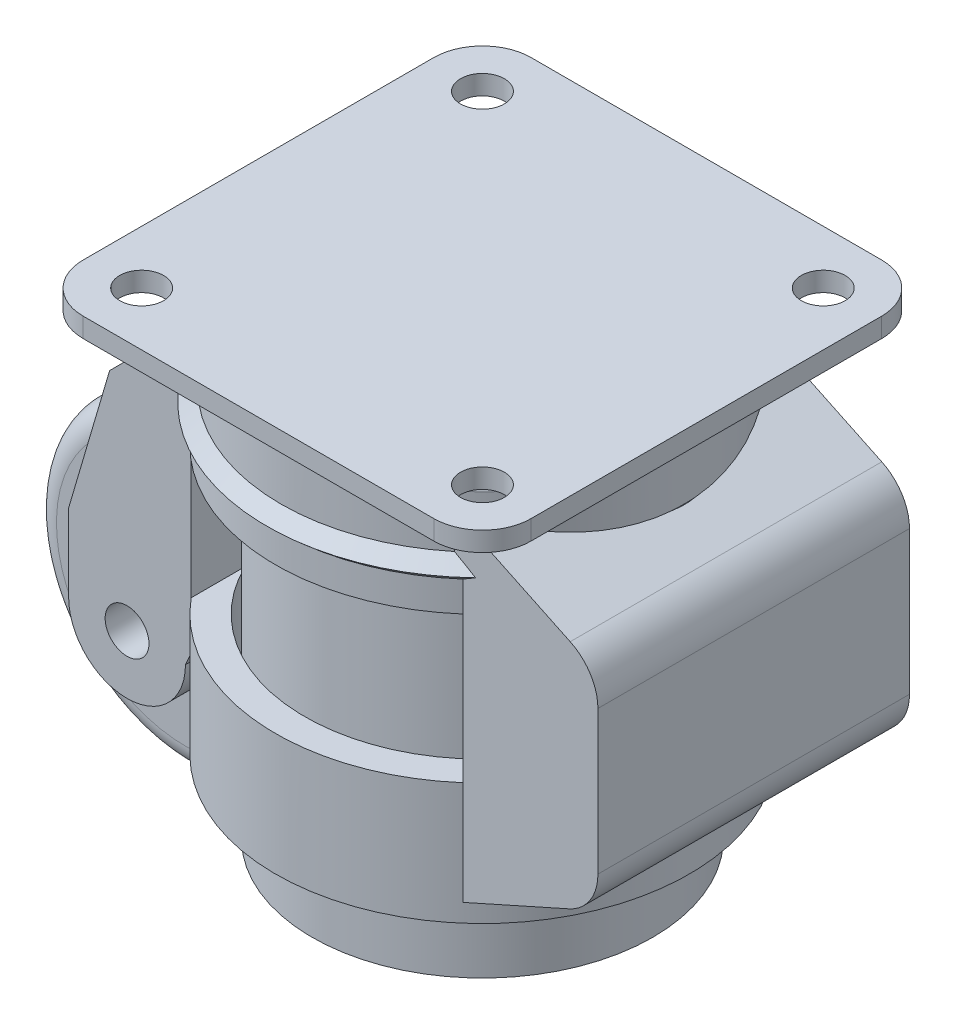
SolidWorks part; units mm, degrees
ref_plane "前视基准面" through (0, 0, 0) normal (0, 0, 1) x (1, 0, 0)
ref_plane "上视基准面" through (0, 0, 0) normal (0, 1, 0) x (1, 0, 0)
ref_plane "右视基准面" through (0, 0, 0) normal (1, 0, 0) x (0, 0, -1)
sketch "草图1" plane through (0, 0, 0) normal (0, 0, 1) x (1, 0, 0)
  line L2 (46, 0) -> (46, 4)
  line L3 (-46, 4) -> (-46, 0)
  line L4 (-46, 0) -> (46, 0)
  line L5 (-46, 4) -> (46, 4)
extrude "凸台-拉伸1" add sketch "草图1" along normal blind 46 and the other way blind 46
sketch "草图2" plane through (0, 4, 0) normal (0, 1, 0) x (1, 0, 0)
  circle A0 centre (35, 35) radius 4.5
  circle A1 centre (-35, 35) radius 4.5
  circle A2 centre (-35, -35) radius 4.5
  circle A3 centre (35, -35) radius 4.5
  dimension "D1" = 35
  dimension "D2" = 35
  dimension "D3" = 2
  dimension "D4" = 2
extrude "切除-拉伸1" cut sketch "草图2" against normal through all
fillet "圆角1" radius 10 4 edges at (46, 2, -46) (-46, 2, -46) (46, 2, 46) (-46, 2, 46)
sketch "草图3" plane through (0, 0, 0) normal (0, 0, 1) x (1, 0, 0)
  line L0 (0, 0) -> (30, 0)
  line L1 (-36, 0) -> (36, 0) construction
  line L2 (30, 0) -> (30, -2)
  line L3 (30, -2) -> (40.3924, -2)
  line L4 (41.3924, -3) -> (41.3924, -13.7394)
  line L6 (42.5, -17.7944) -> (42.5, -79)
  line L7 (41.3924, -13.7394) -> (44.2632, -16.2515)
  line L8 (42.5, -79) -> (0, -79)
  line L9 (0, -79) -> (0, 0)
  line L10 (36, 4) -> (-36, 4) construction
  line L11 (42.5, -17.7944) -> (44.2632, -16.2515)
  arc A0 (41.3924, -3) -> (40.3924, -2) centre (40.3924, -3) ccw
  dimension "D4" = 1
  dimension "D1" = 30
  dimension "D2" = 2
  dimension "D3" = 83
  dimension "D5" = 42.5
revolve "旋转1" add sketch "草图3" angle 360 about L9
sketch "草图4" plane through (0, 0, 0) normal (0, 0, 1) x (1, 0, 0)
  line L0 (-41.3924, -13.7394) -> (-49.5804, -21.9716)
  line L1 (-49.5804, -21.9716) -> (-58, -50.6155)
  line L3 (-41.3924, -13.7394) -> (-44.2632, -16.2515) construction
  line L5 (-27.053, -50.6155) -> (-9.2251, -27.0175)
  line L6 (-9.2251, -27.0175) -> (-28.47, -9.3947)
  line L7 (-28.47, -9.3947) -> (-41.3924, -13.7394)
  line L9 (36, 4) -> (-36, 4) construction
  line L10 (-58, -66.5) -> (-58, -50.6155)
  line L11 (-34, -66.5) -> (-27.053, -50.6155)
  arc A0 (-58, -66.5) -> (-34, -66.5) centre (-46, -66.5) ccw
  dimension "D1" = 70.5
  dimension "D2" = 46
extrude "凸台-拉伸2" add sketch "草图4" along normal blind 27 and the other way blind 27
sketch "草图5" plane through (0, -79, 0) normal (0, -1, 0) x (1, 0, 0)
  circle A0 centre (0, 0) radius 36.5
extrude "切除-拉伸2" cut sketch "草图5" against normal blind 68.6 and the other way blind 32
sketch "草图8" plane through (0, 0, 0) normal (0, 0, 1) x (1, 0, 0)
  line L0 (36, 4) -> (-36, 4) construction
  line L1 (-67.3863, -34) -> (0, -34)
  line L2 (-67.3863, -34) -> (-67.3863, -109.3295)
  line L3 (-67.3863, -109.3295) -> (0, -109.3295)
  line L4 (0, -34) -> (0, -109.3295)
  dimension "D1" = 38
extrude "切除-拉伸3" cut sketch "草图8" against normal blind 15 and the other way blind 15
sketch "草图9" plane through (0, 0, 27) normal (0, 0, 1) x (1, 0, 0)
  circle A0 centre (-46, -66.5) radius 4.5
extrude "切除-拉伸4" cut sketch "草图9" against normal through all
sketch "草图11" plane through (0, 0, 0) normal (0, 0, 1) x (1, 0, 0)
  circle A0 centre (-46, -66.5) radius 31.5
extrude "凸台-拉伸3" add sketch "草图11" along normal blind 15 and the other way blind 15
fillet "圆角2" radius 5 2 edges at (-48.6619, -97.8873, 15) (-48.6619, -97.8873, -15)
sketch "草图13" plane through (0, -79, 0) normal (0, -1, 0) x (1, 0, 0)
  line L0 (-12, 17.5) -> (-30.3109, 17.5)
  line L1 (-12, 17.5) -> (-12, -17.5)
  line L2 (-12, -17.5) -> (-30.3109, -17.5)
  arc A0 (-30.3109, -17.5) -> (-30.3109, 17.5) centre (0, 0) ccw
  dimension "D1" = 17.5
  dimension "D3" = 70
  dimension "D2" = 17.5
  dimension "D4" = 12
sketch "草图14" plane through (0, 0, 0) normal (0, 0, 1) x (1, 0, 0)
  line L0 (22.6517, -4.8219) -> (55.7189, -20.614)
  line L1 (55.7189, -20.614) -> (55.7189, -62.8829)
  line L2 (55.7189, -62.8829) -> (18.46, -79.5439)
  line L3 (18.46, -79.5439) -> (22.6517, -4.8219)
extrude "凸台-拉伸6" add sketch "草图14" along normal blind 32 and the other way blind 32
sketch "草图16" plane through (0, -79, 0) normal (0, -1, 0) x (1, 0, 0)
  line L1 (-22.8896, 28.4309) -> (0.9181, 28.4309)
  line L4 (0.9181, 28.4309) -> (0.9181, -36.4885)
  arc A0 (0.9181, -36.4885) -> (-22.8896, 28.4309) centre (0, 0) ccw
extrude "切除-拉伸6" cut sketch "草图16" against normal up to surface (68.6 mm away) up to face at (-7.0806, -10.4, 0)
sketch "草图17" plane through (0, 0, 32) normal (0, 0, 1) x (1, 0, 0)
  line L0 (-30.3109, -79) -> (35, -79) construction
  line L1 (-2.2409, -79) -> (43.1883, -79)
  line L2 (-2.2409, -79) -> (-2.2409, -96.4908)
  line L3 (-2.2409, -96.4908) -> (43.1883, -96.4908)
  line L4 (43.1883, -79) -> (43.1883, -96.4908)
extrude "切除-拉伸7" cut sketch "草图17" against normal through all
extrude "凸台-拉伸7" add sketch "草图13" along normal blind 15 and the other way blind 64 separate body
fillet "圆角3" radius 10 2 edges at (55.7189, -20.614, 0) (55.7189, -62.8829, 0)
ref_plane "基准面2" through (0, -54, 0) normal (0, -1, 0) x (-1, 0, 0)
sketch "草图18" plane through (0, -54, 0) normal (0, -1, 0) x (-1, 0, 0)
  line L0 (-27.9687, -45.7389) -> (-27.9687, -21.9176)
  line L1 (32.8215, -42.3916) -> (32.8215, -13.6154)
  line L2 (-27.9687, 21.9176) -> (-27.9687, 45.7389)
  line L3 (32.8215, 13.6154) -> (32.8215, 42.3916)
  line L4 (0, 0) -> (-35.1716, 0) construction
  arc A0 (32.8215, 42.3916) -> (-27.9687, 45.7389) centre (0, 0) ccw
  arc A1 (32.8215, 13.6154) -> (-27.9687, 21.9176) centre (0, 0) ccw
  arc A2 (-27.9687, -21.9176) -> (32.8215, -13.6154) centre (0, 0) ccw
  arc A3 (32.8215, -42.3916) -> (-27.9687, -45.7389) centre (0, 0) cw
extrude "切除-拉伸8" cut sketch "草图18" against normal blind 30
